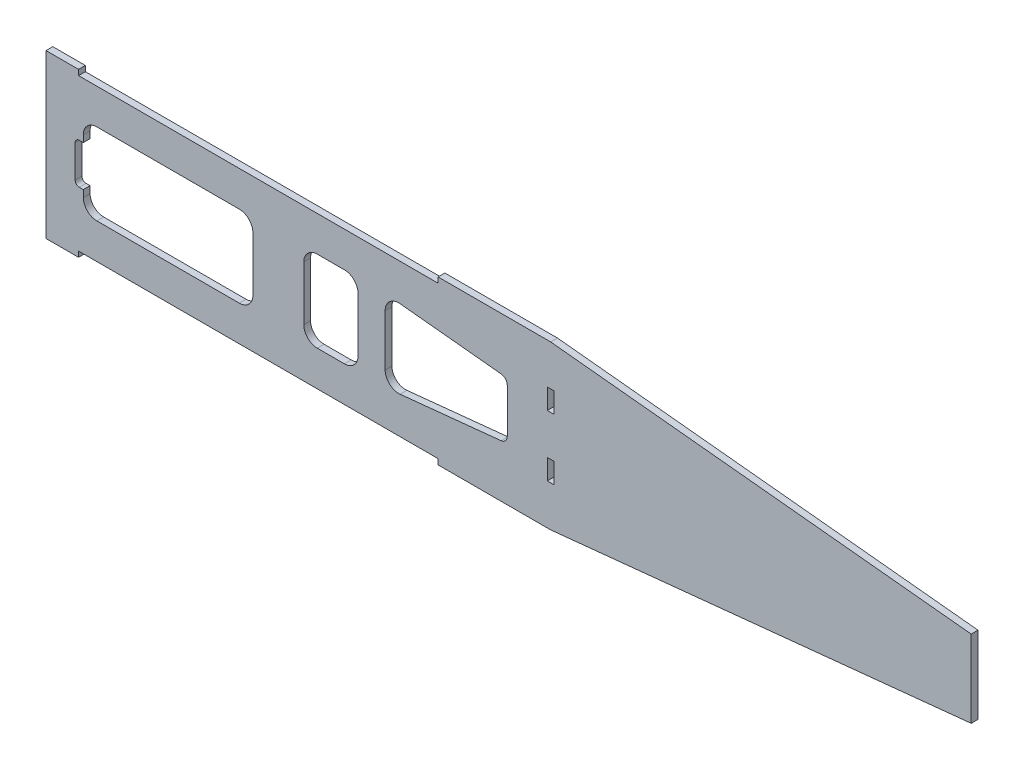
SolidWorks part; units mm, degrees
ref_plane "Ebene vorne" through (0, 0, 0) normal (0, 0, 1) x (1, 0, 0)
ref_plane "Ebene oben" through (0, 0, 0) normal (0, 1, 0) x (1, 0, 0)
ref_plane "Ebene rechts" through (0, 0, 0) normal (1, 0, 0) x (0, 0, -1)
sketch "Skizze1" plane through (0, 0, 0) normal (0, 0, 1) x (1, 0, 0)
  line L0 (0, 0) -> (682, 0) construction
  line L1 (0, 60) -> (0, -60)
  line L2 (0, -60) -> (372, -60)
  line L3 (372, -60) -> (682, -28.5)
  line L4 (682, -28.5) -> (682, 28.5)
  line L5 (372, 60) -> (682, 28.5)
  line L6 (0, 60) -> (372, 60)
  dimension "D1" = 682
  dimension "D2" = 120
  dimension "D3" = 57
  dimension "D4" = 310
extrude "Grundplatte" add sketch "Skizze1" along normal blind 5
sketch "Skizze2" plane through (0, 0, 5) normal (0, 0, 1) x (1, 0, 0)
  line L0 (50, 0) -> (21.5, 0) construction
  line L1 (152.5, 30) -> (27.5, 30)
  line L2 (152.5, 30) -> (152.5, -30)
  line L3 (152.5, -30) -> (27.5, -30)
  line L4 (27.5, 30) -> (27.5, 15)
  line L5 (152.5, 30) -> (27.5, -30) construction
  line L6 (152.5, -30) -> (27.5, 30) construction
  line L7 (21.5, -15) -> (21.5, 15)
  line L8 (21.5, 15) -> (27.5, 15)
  line L9 (21.5, -15) -> (27.5, -15)
  line L10 (27.5, -15) -> (27.5, -30)
  point P0 (90, 0)
  dimension "D1" = 90
  dimension "D2" = 60
  dimension "D3" = 125
  dimension "D4" = 30
  dimension "D5" = 6
extrude "Schnitt-Linear austragen1" cut sketch "Skizze2" against normal through all
fillet "Verrundung1" radius 10 4 edges at (152.5, 30, 2.5) (152.5, -30, 2.5) (27.5, 30, 2.5) (27.5, -30, 2.5)
sketch "Skizze3" plane through (0, 0, 5) normal (0, 0, 1) x (1, 0, 0)
  line L0 (0, 0) -> (682, 0) construction
  line L1 (0, 60) -> (0, -60) construction
  line L2 (682, -28.5) -> (682, 28.5) construction
  line L3 (372, 60) -> (0, 60) construction
  line L4 (24, 60) -> (289, 60)
  line L5 (24, 60) -> (24, 56)
  line L6 (24, 56) -> (289, 56)
  line L7 (289, 60) -> (289, 56)
  line L8 (289, -60) -> (289, -56)
  line L9 (24, -56) -> (289, -56)
  line L10 (24, -60) -> (24, -56)
  line L11 (24, -60) -> (289, -60)
  dimension "D1" = 4
  dimension "D2" = 265
  dimension "D3" = 24
extrude "Ausschnitt_Flächenaufdoppler" cut sketch "Skizze3" against normal through all
sketch "Skizze4" plane through (0, 0, 5) normal (0, 0, 1) x (1, 0, 0)
  line L0 (0, 0) -> (682, 0) construction
  line L1 (682, -28.5) -> (682, 28.5) construction
  line L2 (190, -30) -> (190, 30)
  line L3 (190, 30) -> (230, 30)
  line L4 (230, 30) -> (230, -30)
  line L6 (250, -30) -> (250, 30)
  line L7 (250, 30) -> (340, 20.8548)
  line L8 (340, 20.8548) -> (340, -20.8548)
  line L9 (250, -30) -> (340, -20.8548)
  line L10 (190, -30) -> (230, -30)
  line L11 (682, 28.5) -> (372, 60) construction
  line L13 (0, 60) -> (0, -60) construction
  point P14 (340, 0)
  point P17 (190, 0)
  dimension "D1" = 60
  dimension "D2" = 60
  dimension "D3" = 90
  dimension "D4" = 20
  dimension "D5" = 40
  dimension "D6" = 190
extrude "Ausschnitt Gewicht" cut sketch "Skizze4" against normal through all
fillet "Verrundung2" radius 10 6 edges at (250, -30, 2.5) (250, 30, 2.5) (190, -30, 2.5) (230, -30, 2.5) (230, 30, 2.5) (190, 30, 2.5)
fillet "Verrundung3" radius 5 2 edges at (340, -20.8548, 2.5) (340, 20.8548, 2.5)
fillet "Verrundung4" radius 3 2 edges at (21.5, -15, 2.5) (21.5, 15, 2.5)
sketch "Skizze5" plane through (0, 0, 5) normal (0, 0, 1) x (1, 0, 0)
  line L0 (372, 60) -> (372, 22.5) construction
  line L1 (372, 22.5) -> (372, -22.5) construction
  line L2 (372, -22.5) -> (372, -60) construction
  line L4 (374.5, 30) -> (369.5, 30)
  line L5 (374.5, 30) -> (374.5, 15)
  line L6 (374.5, 15) -> (369.5, 15)
  line L7 (369.5, 30) -> (369.5, 15)
  line L8 (374.5, 30) -> (369.5, 15) construction
  line L9 (374.5, 15) -> (369.5, 30) construction
  line L10 (374.5, -15) -> (369.5, -15)
  line L11 (374.5, -15) -> (374.5, -30)
  line L12 (374.5, -30) -> (369.5, -30)
  line L13 (369.5, -15) -> (369.5, -30)
  line L14 (374.5, -15) -> (369.5, -30) construction
  line L15 (374.5, -30) -> (369.5, -15) construction
  dimension "D1" = 30
  dimension "D2" = 5
  dimension "D3" = 15
extrude "Schnitt-Linear austragen2" cut sketch "Skizze5" against normal through all
